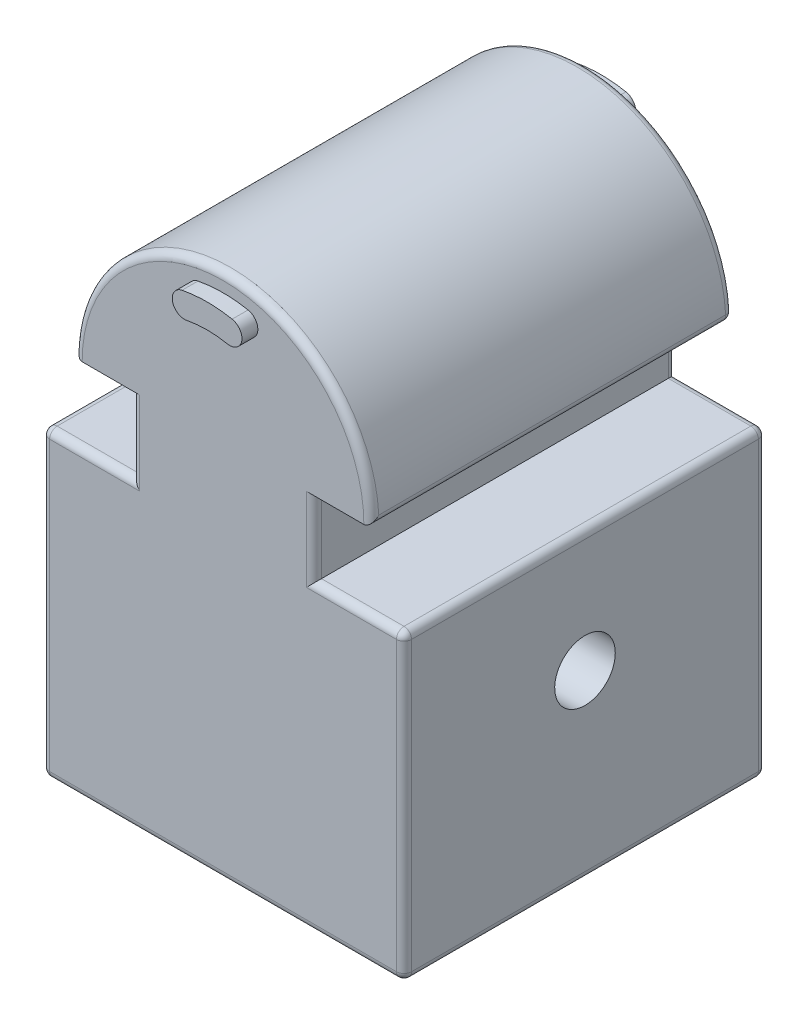
SolidWorks part; units mm, degrees
ref_plane "Front Plane" through (0, 0, 0) normal (0, 0, 1) x (1, 0, 0)
ref_plane "Top Plane" through (0, 0, 0) normal (0, 1, 0) x (1, 0, 0)
ref_plane "Right Plane" through (0, 0, 0) normal (1, 0, 0) x (0, 0, -1)
sketch "Sketch1" plane through (0, 0, 0) normal (0, 0, 1) x (1, 0, 0)
  line L0 (-12.446, 0) -> (12.446, 0)
  line L1 (0, 0) -> (-7.62, 0) construction
  line L2 (0, 9.906) -> (-1.905, 9.906) construction
  line L3 (-7.62, 0) -> (7.62, 0)
  line L7 (0, 9.906) -> (1.905, 9.906) construction
  line L8 (-7.62, -6.35) -> (-15.1765, -6.35)
  line L9 (7.62, -6.35) -> (15.1765, -6.35)
  line L10 (-7.62, -6.35) -> (-7.62, 0)
  line L12 (-15.1765, -6.35) -> (-15.1765, -31.75)
  line L15 (7.62, -6.35) -> (7.62, 0)
  line L16 (-15.1765, -31.75) -> (15.1765, -31.75)
  line L17 (15.1765, -31.75) -> (15.1765, -6.35)
  arc A0 (12.446, 0) -> (-12.446, 0) centre (0, 0) ccw
  arc A1 (8.636, 0) -> (-8.636, 0) centre (0, 0) ccw
  arc A2 (11.176, 0) -> (-11.176, 0) centre (0, 0) ccw
  arc A3 (11.049, 0) -> (-11.049, 0) centre (0, 0) ccw
  arc A4 (8.89, 0) -> (-8.89, 0) centre (0, 0) ccw
  circle A5 centre (0, 0) radius 11.176 construction
  circle A6 centre (0, 0) radius 11.049 construction
  circle A7 centre (0, 0) radius 8.89 construction
  circle A8 centre (0, 0) radius 8.636 construction
  arc A10 (9.906, 0) -> (-9.906, 0) centre (0, 0) ccw construction
  arc A11 (-1.905, 9.7211) -> (1.905, 9.7211) centre (0, 0) cw construction
  arc A12 (2.1004, 10.7181) -> (-2.1004, 10.7181) centre (0, 0) ccw
  arc A13 (1.7096, 8.7241) -> (-1.7096, 8.7241) centre (0, 0) ccw
  arc A14 (1.7096, 8.7241) -> (2.1004, 10.7181) centre (1.905, 9.7211) ccw
  arc A15 (-2.1004, 10.7181) -> (-1.7096, 8.7241) centre (-1.905, 9.7211) ccw
  arc A16 (-1.905, 9.7211) -> (1.905, 9.7211) centre (0, 0) cw construction
  arc A17 (2.1004, 10.7181) -> (-2.1004, 10.7181) centre (0, 0) ccw
  arc A18 (1.7096, 8.7241) -> (-1.7096, 8.7241) centre (0, 0) ccw
  arc A19 (1.7096, 8.7241) -> (2.1004, 10.7181) centre (1.905, 9.7211) ccw
  arc A20 (-2.1004, 10.7181) -> (-1.7096, 8.7241) centre (-1.905, 9.7211) ccw
  point P31 (0, 9.906)
  point P39 (0, 9.906)
  dimension "D1" = 24.892
  dimension "D2" = 22.352
  dimension "D3" = 17.272
  dimension "D8" = 9.906
  dimension "D11" = 8.89
  dimension "D12" = 10.922
  dimension "D4" = 7.62
  dimension "D7" = 0.254
  dimension "D9" = 1.905
  dimension "D10" = 1.905
  dimension "D14" = 7.5565
  dimension "D5" = 7.5565
extrude "Main Body Extrude" add sketch "Sketch1" along normal mid plane 30.353 contours L0 | A12 A15 A4 A14 | L0 A0 region at (0, 9.8081, 0) region at (0, -17.2796, 0)
extrude "Slot Extrude" add sketch "Sketch1<4>" along normal mid plane 33.02 contours A12 A15 A4 A14 region at (0, 9.8081, 0)
sketch "Sketch1<4>" plane through (0, 0, 0) normal (0, 0, 1) x (1, 0, 0) same geometry as "Sketch1"
sketch "Sketch2" plane through (0, -31.75, 0) normal (0, -1, 0) x (1, 0, 0)
  line L1 (-9.525, -9.525) -> (9.525, -9.525)
  line L2 (-9.525, -9.525) -> (-9.525, 9.525)
  line L3 (-9.525, 9.525) -> (9.525, 9.525)
  line L4 (9.525, -9.525) -> (9.525, 9.525)
  line L5 (-9.525, -9.525) -> (9.525, 9.525) construction
  line L6 (-9.525, 9.525) -> (9.525, -9.525) construction
  point P0 (0, 0)
  dimension "D1" = 19.05
  dimension "D2" = 19.05
extrude "Foot Connection Cut" cut sketch "Sketch2" against normal blind 22.86
sketch "Sketch4" plane through (-9.525, 0, 0) normal (1, 0, 0) x (0, 0, -1)
  line L0 (0, -8.89) -> (0, -16.51)
  line L5 (-9.525, -31.75) -> (9.525, -31.75)
  line L6 (9.525, -31.75) -> (9.525, -8.89)
  line L7 (9.525, -8.89) -> (-9.525, -8.89)
  line L8 (-9.525, -8.89) -> (-9.525, -31.75)
  line L9 (-9.525, -31.75) -> (9.525, -31.75)
  line L10 (9.525, -31.75) -> (9.525, -8.89)
  line L11 (9.525, -8.89) -> (-9.525, -8.89)
  line L12 (-9.525, -8.89) -> (-9.525, -31.75)
  circle A0 centre (0, -16.51) radius 2.54
  dimension "D3" = 5.08
  dimension "D1" = 7.62
  dimension "D2" = 0
extrude "Pinhole Cut" cut sketch "Sketch4" against normal mid plane 50.8 contours A0 region at (-9.525, -14.7647, -1.7453)
fillet "Fillet1" radius 0.635 24 edges at (11.3983, -6.35, 15.1765) (12.446, 0, 0) (15.1765, -6.35, 0) (7.62, -3.175, 15.1765) (-11.3982, -6.35, 15.1765) (-15.1765, -6.35, 0) (-7.62, -3.175, 15.1765) (-12.446, 0, 0) (0, 12.446, 15.1765) (11.3983, -6.35, -15.1765) (7.62, -3.175, -15.1765) (10.033, 0, -15.1765) (-10.033, 0, -15.1765) (-7.62, -3.175, -15.1765) (-11.3982, -6.35, -15.1765) (0, 12.446, -15.1765) (15.1765, -31.75, 0) (-15.1765, -31.75, 0) (0, -31.75, 15.1765) (0, -31.75, -15.1765) (-15.1765, -19.05, -15.1765) (-15.1765, -19.05, 15.1765) (15.1765, -19.05, 15.1765) (15.1765, -19.05, -15.1765)
chamfer "Chamfer2" distance 2.54 angle 45 4 edges at (-9.525, -20.32, -9.525) (-9.525, -20.32, 9.525) (9.525, -20.32, -9.525) (9.525, -20.32, 9.525)
chamfer "Chamfer1" distance 2.54 angle 45 8 edges at (9.525, -31.75, 0) (0, -31.75, -9.525) (0, -31.75, 9.525) (-9.525, -31.75, 0) (-8.255, -31.75, 8.255) (8.255, -31.75, 8.255) (8.255, -31.75, -8.255) (-8.255, -31.75, -8.255)
equation "\"InnerBaseDiameter\"=0.98"
equation "\"InnerBaseOuterGroove\"= \"InnerBaseDiameter\" - 0.1"
equation "\"InnerHingeInnerCurve\"= 1"
equation "\"InnerHingeOuterCurve\" = \"InnerHingeInnerCurve\" + 0.1"
equation "\"InnerBaseInnerGroove\"= \"InnerBaseOuterGroove\" - 0.2"
equation "\"InnerHingeWidth\"= 1.45"
equation "\"OuterBaseInnerGroove\"= \"OuterBaseOuterGroove\" - 0.25"
equation "\"OuterBaseDiameter\"= ( ( \"InnerHingeOuterCurve\" / 2 ) ^ 2 + ( \"InnerHingeLength\" / 2 ) ^ 2 ) ^ 0.5 * 2"
equation "\"InnerHingeLength\"=1.2"
equation "\"OuterBaseOuterGroove\" = \"OuterBaseDiameter\" - 0.2"
equation "\"D1@Sketch1\"=\"InnerBaseDiameter\""
equation "\"D2@Sketch1\"=\"InnerBaseOuterGroove\""
equation "\"D3@Sketch1\"=\"InnerBaseInnerGroove\""
equation "\"D8@Sketch1\"=\"InnerBaseOuterGroove\"  * 0.25 +\"InnerBaseInnerGroove\" * 0.25"
equation "\"D11@Sketch1\"=\"InnerBaseInnerGroove\" *0.5 +0.01"
equation "\"D12@Sketch1\"=\"InnerBaseOuterGroove\"*0.5 -0.01"
